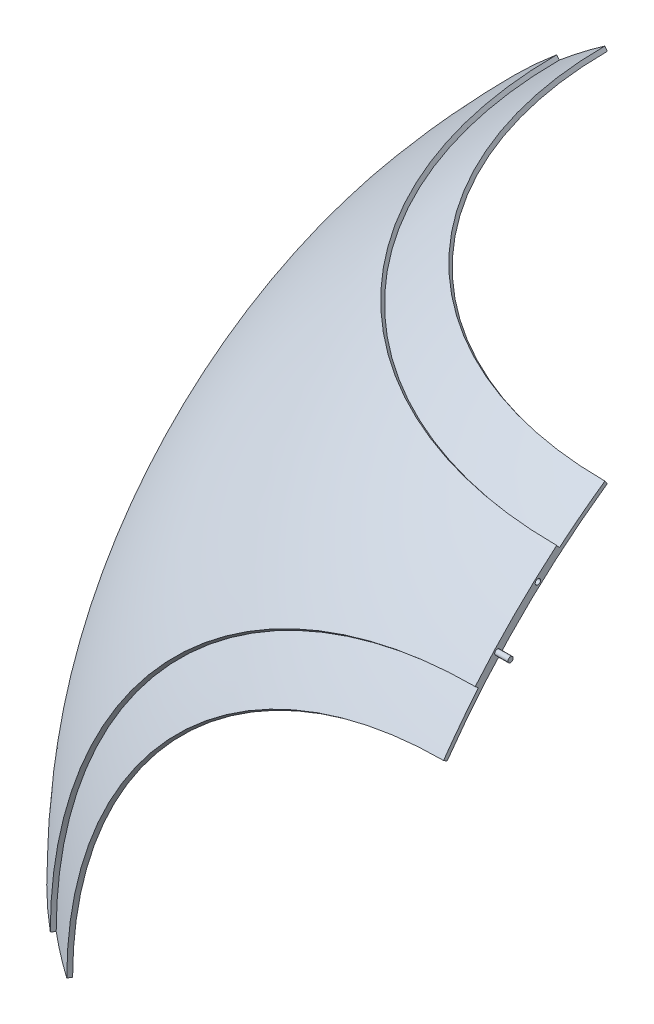
SolidWorks part; units mm, degrees
ref_plane "Front Plane" through (0, 0, 0) normal (0, 0, 1) x (1, 0, 0)
ref_plane "Top Plane" through (0, 0, 0) normal (0, 1, 0) x (1, 0, 0)
ref_plane "Right Plane" through (0, 0, 0) normal (1, 0, 0) x (0, 0, -1)
sketch "Sketch1" plane through (0, 0, 0) normal (0, 0, 1) x (1, 0, 0)
  line L0 (0, 0) -> (0, 309.9271)
  line L1 (0, 309.9271) -> (0, 0)
  line L2 (-246.825, 0) -> (-250, 0)
  line L3 (-141.573, 202.1872) -> (-142.4836, 203.4876)
  line L4 (-159.6765, 190.295) -> (-160.6969, 191.5111)
  arc A0 (-160.6969, 191.5111) -> (-250, 0) centre (0, 0) ccw
  arc A1 (-141.573, 202.1872) -> (-246.825, 0) centre (0, 0) ccw
  arc A2 (-142.4836, 203.4876) -> (-159.6765, 190.295) centre (0, 0) ccw
  dimension "D1" = 500
  dimension "D2" = 493.65
  dimension "D3" = 496.825
  dimension "D4" = 35
  dimension "D5" = 5
revolve "Revolve1" add sketch "Sketch1" angle 90 about L0 region at (-248.4125, 2.3057, 0)
sketch "Sketch3" plane through (0, 0, 0) normal (1, 0, 0) x (0, 0, -1)
  line L0 (-246.825, 0) -> (-250, 0)
  line L1 (-202.1872, 141.573) -> (-203.4876, 142.4836)
  line L2 (-190.295, 159.6765) -> (-191.5111, 160.6969)
  arc A0 (-190.295, 159.6765) -> (-203.4876, 142.4836) centre (0, 0) ccw
  arc A1 (-141.573, 202.1872) -> (-246.825, 0) centre (0, 0) ccw construction
  arc A2 (-202.1872, 141.573) -> (-246.825, 0) centre (0, 0) ccw
  arc A3 (-160.6969, 191.5111) -> (-250, 0) centre (0, 0) ccw construction
  arc A4 (-191.5111, 160.6969) -> (-250, 0) centre (0, 0) ccw
  dimension "D1" = 496.825
  dimension "D2" = 5
  dimension "D3" = 35
revolve "Cut-Revolve1" cut sketch "Sketch3" angle 360 about L0
sketch "Sketch4" plane through (0, 0, 0) normal (0, 0, -1) x (-1, 0, 0)
  line L0 (246.825, 0) -> (250, 0)
  line L1 (202.1872, 141.573) -> (203.4876, 142.4836)
  line L2 (190.295, 159.6765) -> (191.5111, 160.6969)
  arc A0 (203.4876, 142.4836) -> (190.295, 159.6765) centre (0, 0) ccw
  arc A1 (246.825, 0) -> (141.573, 202.1872) centre (0, 0) ccw construction
  arc A2 (246.825, 0) -> (202.1872, 141.573) centre (0, 0) ccw
  arc A3 (250, 0) -> (160.6969, 191.5111) centre (0, 0) ccw construction
  arc A4 (250, 0) -> (191.5111, 160.6969) centre (0, 0) ccw
  dimension "D1" = 496.825
  dimension "D2" = 5
  dimension "D3" = 35
revolve "Cut-Revolve2" cut sketch "Sketch4" angle 360 about L0
sketch "Sketch5" plane through (0, 0, 0) normal (0, 0, -1) x (-1, 0, 0)
  circle A1 centre (167.8251, 183.1489) radius 1
  circle A2 centre (183.1489, 167.8251) radius 1
  dimension "D1" = 2
  dimension "D2" = 2
extrude "Boss-Extrude2" add sketch "Sketch5" along normal blind 5 contours A1
extrude "Cut-Extrude1" cut sketch "Sketch5<3>" against normal blind 5 contours A2 region at (-183.1489, 167.8251, 0)
sketch "Sketch5<3>" plane through (0, 0, 0) normal (0, 0, -1) x (-1, 0, 0) same geometry as "Sketch5"
sketch "Sketch7" plane through (0, 0, 0) normal (1, 0, 0) x (0, 0, -1)
  circle A1 centre (-183.1489, 167.8251) radius 1
  circle A2 centre (-167.8251, 183.1489) radius 1
  dimension "D1" = 2
  dimension "D2" = 2
extrude "Boss-Extrude3" add sketch "Sketch7" along normal blind 5 contours A1 region at (0, 167.8251, 183.1489)
extrude "Cut-Extrude2" cut sketch "Sketch7<3>" against normal blind 5 contours A2 region at (0, 183.1489, 167.8251)
sketch "Sketch7<3>" plane through (0, 0, 0) normal (1, 0, 0) x (0, 0, -1) same geometry as "Sketch7"
sketch "Sketch9" plane through (0, 0, 0) normal (0, -1, 0) x (1, 0, 0)
  circle A0 centre (0, 0) radius 248.4125
  circle A1 centre (-183.1489, 167.8251) radius 1
  circle A2 centre (-167.8251, 183.1489) radius 1
  dimension "D1" = 2
  dimension "D2" = 2
  dimension "D3" = 2.5
  dimension "D4" = 5
extrude "Boss-Extrude4" add sketch "Sketch9" along normal blind 5 contours A0 A1 | A0 A1 region at (-183.4615, 0, 168.1115) region at (-182.8357, 0, 167.5381)
extrude "Cut-Extrude3" cut sketch "Sketch9<3>" against normal blind 5 contours A0 A2 | A0 A2 region at (-167.5381, 0, 182.8357) region at (-168.1115, 0, 183.4615)
sketch "Sketch9<3>" plane through (0, 0, 0) normal (0, -1, 0) x (1, 0, 0) same geometry as "Sketch9"
